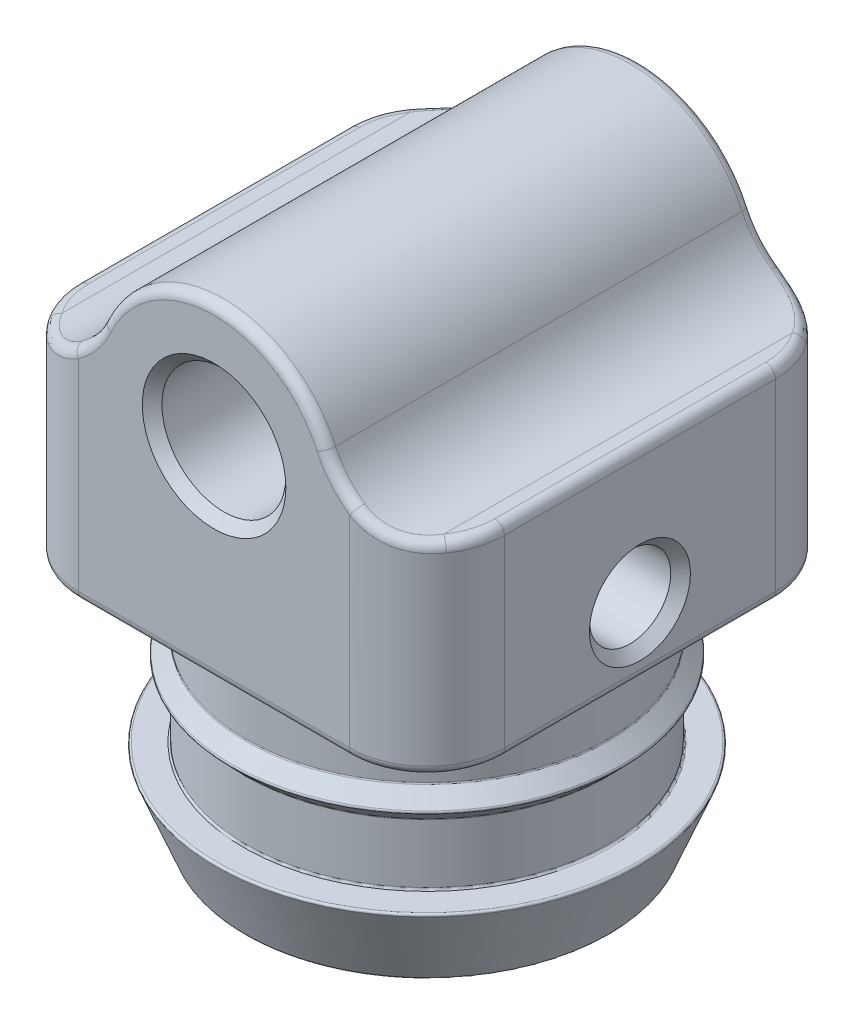
SolidWorks part; units mm, degrees
ref_plane "Front Plane" through (0, 0, 0) normal (0, 0, 1) x (1, 0, 0)
ref_plane "Top Plane" through (0, 0, 0) normal (0, 1, 0) x (1, 0, 0)
ref_plane "Right Plane" through (0, 0, 0) normal (1, 0, 0) x (0, 0, -1)
sketch "Sketch1" plane through (0, 0, 0) normal (0, 0, 1) x (1, 0, 0)
  line L3 (0, 0) -> (0, -10.5) construction
  line L4 (-11, 0) -> (-6.35, 0)
  line L5 (-11, 0) -> (-11, -10.5)
  line L6 (-11, -10.5) -> (11, -10.5)
  line L7 (11, 0) -> (11, -10.5)
  line L8 (6.35, 0) -> (11, 0)
  circle A0 centre (0, 0) radius 3.2
  arc A1 (6.35, 0) -> (-6.35, 0) centre (0, 0) ccw
  dimension "D1" = 6.4
  dimension "D2" = 12.7
  dimension "D4" = 22
  dimension "D5" = 10.5
extrude "Boss-Extrude1" add sketch "Sketch1" along normal mid plane 22
sketch3d "3DSketch1" plane through (0, 0, 0) normal (0, 0, 1) x (1, 0, 0)
  dimension "D1" = 12.7
sketch "Sketch2" plane through (0, 0, 0) normal (0, 0, 1) x (1, 0, 0)
  line L0 (0, 9.544) -> (0, -9.544) construction
  line L1 (0, -10) -> (9.365, -10)
  line L4 (0, -22.7) -> (9.365, -22.7)
  line L10 (0, -22.7) -> (0, -10)
  line L11 (9.365, -22.7) -> (10.9525, -18.7312)
  line L12 (10.9525, -18.7312) -> (9.365, -18.7312)
  line L13 (9.365, -18.7312) -> (9.365, -15.5562)
  line L14 (9.365, -15.5562) -> (10.1587, -14.7625)
  line L15 (10.1587, -14.7625) -> (9.365, -13.9687)
  line L16 (10.1587, -14.7625) -> (9.365, -14.7625) construction
  line L17 (9.365, -13.9687) -> (9.365, -10)
  dimension "D1" = 18.73
  dimension "D2" = 12.7
  dimension "D3" = 1.5875
  dimension "D4" = 3.9688
  dimension "D5" = 0.7937
  dimension "D6" = 7.9375
  dimension "D7" = 10
revolve "Revolve1" add sketch "Sketch2" angle 360 about L0
sketch "Sketch3" plane through (0, -22.7, 0) normal (0, -1, 0) x (1, 0, 0)
  circle A0 centre (0, 0) radius 4
  dimension "D1" = 8
extrude "Cut-Extrude1" cut sketch "Sketch3" against normal blind 18 contours A0
hole_wizard "M5x0.8 Tapped Hole1" positions "Sketch4" profile "Sketch5" tap size "M5x0.8" standard "ANSI Metric" end condition up to next
sketch "Sketch4" plane through (11, 0, 0) normal (1, 0, 0) x (0, 0, -1)
  point P0 (0, -7)
  dimension "D1" = 7
cosmetic thread "Hole Thread1" parameters "D2"=5
sketch "Sketch5" plane through (11, -7, 0) normal (0, 1, 0) x (0, 0, -1)
  line L0 (0, 0) -> (0, 7)
  line L1 (0, 7) -> (2.1, 7)
  line L2 (2.1, 7) -> (2.1, 0)
  line L5 (2.1, 0) -> (0, 0)
  line L11 (0, -6.35) -> (0, 107.95) construction
  dimension "Thru Tap Drill Dia." = 4.2
  dimension "Thru Tap Drill Depth" = 7
fillet "Fillet3" radius 0.0992 10 edges at (-10.9525, -18.7312, 0) (-10.1587, -14.7625, 0) (4, -22.7, 0) (4, -4.7, 0) (3.9957, -9.0917, -0.1863) (-9.365, -22.7, 0) (-9.365, -10.5, 0) (-9.365, -15.5562, 0) (-9.365, -13.9688, 0) (-9.365, -18.7312, 0)
chamfer "Chamfer1" distance 0.508 angle 45 3 edges at (3.2, 0, -11) (3.2, 0, 11) (11, -7, -2.1)
fillet "Fillet7" radius 4.5 2 edges at (-6.35, 0, 0) (6.35, 0, 0)
fillet "Fillet6" radius 4 4 edges at (11, -5.25, -11) (-11, -5.25, -11) (-11, -5.25, 11) (11, -5.25, 11)
fillet "Fillet8" radius 0.5 24 edges at (-9.8284, -10.5, 9.8284) (-11, -10.5, 0) (-9.8284, -10.5, -9.8284) (0, -10.5, -11) (9.8284, -10.5, -9.8284) (11, -10.5, 0) (9.8284, -10.5, 9.8284) (10.7075, 0, 8.5015) (8.9278, 0.1004, 10.5048) (6.2987, 1.7659, 11) (0, 6.35, 11) (-6.2987, 1.7659, 11) (-8.0042, 0.4063, 10.8719) (-10.7075, 0, 8.5015) (-11, 0, 0) (-10.7075, 0, -8.5015) (-8.9278, 0.1004, -10.5048) (-6.2987, 1.7659, -11) (0, 6.35, -11) (6.2987, 1.7659, -11) (8.0042, 0.4063, -10.8719) (10.7075, 0, -8.5015) (0, -10.5, 11) (11, 0, 0)
